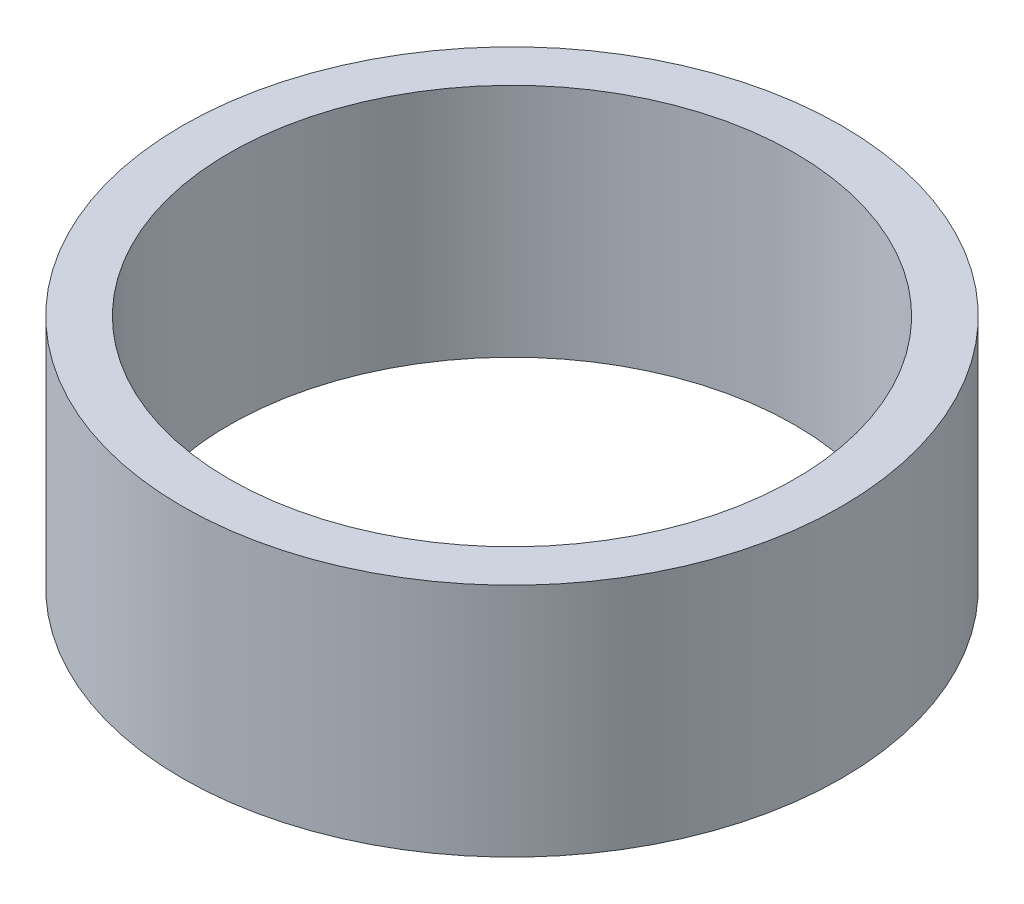
SolidWorks part; units mm, degrees
ref_plane "Front Plane" through (0, 0, 0) normal (0, 0, 1) x (1, 0, 0)
ref_plane "Top Plane" through (0, 0, 0) normal (0, 1, 0) x (1, 0, 0)
ref_plane "Right Plane" through (0, 0, 0) normal (1, 0, 0) x (0, 0, -1)
sketch "Sketch1" plane through (0, 0, 0) normal (0, 1, 0) x (1, 0, 0)
  circle A0 centre (0, 0) radius 6
  dimension "D1" = 12
extrude "Extrude-Thin1" add sketch "Sketch1" along normal blind 5 thin thin type one direction wall 1
